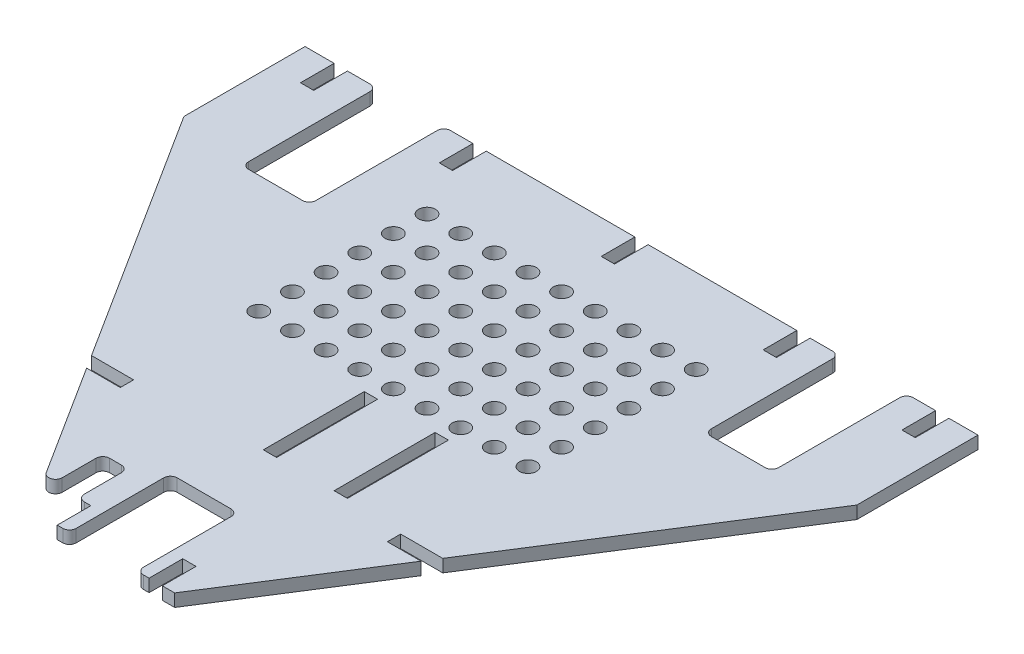
SolidWorks part; units mm, degrees
material "Corrugated Paper"
ref_plane "Front Plane" through (0, 0, 0) normal (0, 0, 1) x (1, 0, 0)
ref_plane "Top Plane" through (0, 0, 0) normal (0, 1, 0) x (1, 0, 0)
ref_plane "Right Plane" through (0, 0, 0) normal (1, 0, 0) x (0, 0, -1)
sketch "Sketch1" plane through (0, 0, 0) normal (0, 1, 0) x (1, 0, 0)
  line L0 (0, 0) -> (0, -142.875) construction
  line L1 (12.7, -63.5) -> (-12.7, -63.5)
  line L2 (-12.7, -63.5) -> (-12.7, -101.6)
  line L3 (-12.7, -101.6) -> (-17.3355, -101.6)
  line L4 (-26.9875, -101.6) -> (-127, 55.88)
  line L5 (-127, 55.88) -> (-127, 101.6)
  line L6 (-127, 101.6) -> (-116.0145, 101.6)
  line L7 (-100.0125, 101.6) -> (-100.0125, 50.8)
  line L9 (-100.0125, 50.8) -> (-74.6125, 50.8)
  line L10 (-74.6125, 50.8) -> (-74.6125, 101.6)
  line L11 (-74.6125, 101.6) -> (-63.627, 101.6)
  line L13 (74.6125, 50.8) -> (74.6125, 101.6)
  line L14 (100.0125, 50.8) -> (74.6125, 50.8)
  line L15 (100.0125, 101.6) -> (100.0125, 50.8)
  line L16 (127, 101.6) -> (116.0145, 101.6)
  line L17 (127, 55.88) -> (127, 101.6)
  line L18 (26.9875, -101.6) -> (127, 55.88)
  line L19 (12.7, -101.6) -> (17.3355, -101.6)
  line L20 (12.7, -63.5) -> (12.7, -101.6)
  line L21 (-127, 101.6) -> (127, -101.6) construction
  line L22 (-22.352, -101.6) -> (-26.9875, -101.6)
  line L24 (-22.352, -101.6) -> (-22.352, -88.9)
  line L25 (-22.352, -88.9) -> (-17.3355, -88.9)
  line L26 (-17.3355, -101.6) -> (-17.3355, -88.9)
  line L27 (22.352, -101.6) -> (22.352, -88.9)
  line L28 (22.352, -88.9) -> (17.3355, -88.9)
  line L29 (17.3355, -101.6) -> (17.3355, -88.9)
  line L30 (22.352, -101.6) -> (26.9875, -101.6)
  line L31 (-87.3125, 50.8) -> (-87.3125, 101.6) construction
  line L32 (-110.998, 101.6) -> (-100.0125, 101.6)
  line L34 (-116.0145, 101.6) -> (-116.0145, 88.9)
  line L35 (-116.0145, 88.9) -> (-110.998, 88.9)
  line L36 (-110.998, 101.6) -> (-110.998, 88.9)
  line L37 (-58.6105, 101.6) -> (-58.6105, 88.9)
  line L38 (-58.6105, 88.9) -> (-63.627, 88.9)
  line L39 (-63.627, 101.6) -> (-63.627, 88.9)
  line L40 (-58.6105, 101.6) -> (58.6105, 101.6)
  line L41 (116.0145, 101.6) -> (116.0145, 88.9)
  line L42 (116.0145, 88.9) -> (110.998, 88.9)
  line L43 (110.998, 101.6) -> (110.998, 88.9)
  line L44 (58.6105, 101.6) -> (58.6105, 88.9)
  line L45 (63.627, 101.6) -> (63.627, 88.9)
  line L46 (58.6105, 88.9) -> (63.627, 88.9)
  line L47 (63.627, 101.6) -> (74.6125, 101.6)
  line L48 (110.998, 101.6) -> (100.0125, 101.6)
  point P26 (0, -63.5)
  dimension "D2" = 25.4
  dimension "D3" = 254
  dimension "D5" = 38.1
  dimension "D6" = 50.8
  dimension "D7" = 203.2
  dimension "D8" = 45.72
  dimension "D9" = 26.9875
  dimension "D4" = 14.2875
  dimension "D10" = 5.0165
  dimension "D11" = 12.7
  dimension "D12" = 5.0165
extrude "Boss-Extrude1" add sketch "Sketch1" along normal blind 4.7625 contours L13 L47 L45 L46 L44 L40 L37 L38 L39 L11 L10 L9 L7 L32 L36 L35 L34 L6 L5 L4 L22 L24 L25 L26 L3 L2 L1 L20 L19 L29 L28 L27 L30 L18 L17 L16 L41 L42 L43 L48 L15 L14
sketch "Sketch2" plane through (0, 4.7625, 0) normal (0, 1, 0) x (1, 0, 0)
  line L0 (12.827, 0) -> (12.827, 54.8341) construction
  line L5 (-7.8105, -1021.0759) -> (-7.8105, 48978.9241) construction
  line L6 (-58.6105, 88.9) -> (-63.627, 88.9) construction
  line L7 (-3.048, 0) -> (1.9685, 0)
  line L8 (-3.048, 0) -> (-3.048, -38.1)
  line L9 (-3.048, -38.1) -> (1.9685, -38.1)
  line L10 (1.9685, 0) -> (1.9685, -38.1)
  line L11 (-22.352, -101.6) -> (-31.877, -101.6)
  line L12 (23.6855, 0) -> (23.6855, -38.1)
  line L13 (28.702, -38.1) -> (23.6855, -38.1)
  line L14 (28.702, 0) -> (28.702, -38.1)
  line L15 (28.702, 0) -> (23.6855, 0)
  line L16 (-22.352, -101.6) -> (-22.352, -69.85)
  line L17 (12.7, -63.5) -> (-12.7, -63.5) construction
  line L18 (-22.352, -69.85) -> (-31.877, -69.85)
  line L19 (-31.877, -101.6) -> (-31.877, -69.85)
  line L20 (-17.3355, -101.6) -> (-17.3355, -88.9) construction
  dimension "D2" = 25.4
  dimension "D3" = 31.75
  dimension "D1" = 38.1
  dimension "D5" = 9.525
  dimension "D6" = 31.75
  dimension "D7" = 9.525
  dimension "D4" = 9.525
extrude "Cut-Extrude1" cut sketch "Sketch2" against normal through all
fillet "Fillet1" radius 2.54 4 edges at (-22.352, 2.3813, 88.9) (-31.877, 2.3813, 93.901) (-22.352, 2.3813, 69.85) (-31.877, 2.3813, 69.85)
fillet "Fillet2" radius 2.54 12 edges at (-12.7, 2.3813, 101.6) (12.7, 2.3813, 101.6) (12.7, 2.3813, 63.5) (-12.7, 2.3813, 63.5) (100.0125, 2.3813, -101.6) (100.0125, 2.3813, -50.8) (74.6125, 2.3813, -101.6) (74.6125, 2.3813, -50.8) (-100.0125, 2.3813, -101.6) (-74.6125, 2.3813, -101.6) (-74.6125, 2.3813, -50.8) (-100.0125, 2.3813, -50.8)
sketch "Sketch3" plane through (0, 4.7625, 0) normal (0, 1, 0) x (1, 0, 0)
  line L0 (-74.6125, 53.34) -> (-74.6125, 99.06) construction
  line L1 (-58.6105, 88.9) -> (-63.627, 88.9) construction
  circle A0 centre (-49.2125, 69.85) radius 3.175
  dimension "D1" = 6.35
  dimension "D2" = 25.4
  dimension "D3" = 19.05
extrude "Cut-Extrude2" cut sketch "Sketch3" against normal through all
pattern_linear "LPattern1" count 9 spacing 12.7 along (1, 0, 0) count 6 spacing 12.7 along (0, 0, 1) of "Cut-Extrude2"
sketch "Sketch4" plane through (0, 4.7625, 0) normal (0, 1, 0) x (1, 0, 0)
  line L0 (0, -164.31) -> (0, 101.6) construction
  line L1 (-63.105, 101.6) -> (63.105, 101.6) construction
  line L2 (-63.105, 101.6) -> (-63.105, -164.31) construction
  line L3 (-63.105, -164.31) -> (63.105, -164.31) construction
  line L4 (63.105, 101.6) -> (63.105, -164.31) construction
  line L5 (26.9875, -101.6) -> (127, 55.88) construction
  line L6 (66.2909, -39.7128) -> (50.405, -39.7128)
  line L7 (66.2909, -39.7128) -> (66.2909, -44.7293)
  line L8 (66.2909, -44.7293) -> (50.405, -44.7293)
  line L9 (50.405, -39.7128) -> (50.405, -44.7293)
  line L10 (-50.405, -39.7128) -> (-50.405, -44.7293)
  line L11 (-66.2909, -44.7293) -> (-50.405, -44.7293)
  line L12 (-66.2909, -39.7128) -> (-66.2909, -44.7293)
  line L13 (-66.2909, -39.7128) -> (-50.405, -39.7128)
  line L14 (-58.6105, 101.6) -> (58.6105, 101.6) construction
  line L15 (-2.5082, 101.6) -> (2.5082, 101.6)
  line L16 (-2.5082, 101.6) -> (-2.5083, 88.9)
  line L17 (-2.5083, 88.9) -> (2.5083, 88.9)
  line L18 (2.5082, 101.6) -> (2.5083, 88.9)
  point P8 (63.105, -44.7293)
  point P11 (0, 101.6)
  dimension "D1" = 265.91
  dimension "D2" = 126.21
  dimension "D5" = 5.0165
  dimension "D6" = 12.7
  dimension "D4" = 12.7
  dimension "D3" = 5.0165
extrude "Cut-Extrude3" cut sketch "Sketch4" against normal through all
equation "\"D1@Boss-Extrude1\" = \"thick\""
equation "\"D4@Sketch1\" = \"thick\" * 3"
equation "\"D10@Sketch1\"=\"thick\"+\"clear\""
equation "\"D9@Sketch1\" = \"thick\" * 3 + 0.5"
equation "\"D12@Sketch1\"=\"thick\"+\"clear\""
equation "\"D3@Sketch2\"=\"MotorLength@Motor-1.Part\""
equation "\"D1@Sketch2\" =  ( \"MotorDiameter@Motor-1.Part\" + 0.5 ) "
equation "\"rodThick\"= 3/16in"
equation "\"thick\"= 3/16in"
equation "\"D5@Sketch2\"=2*\"thick\""
equation "\"clear\"= 0.01in"
equation "\"D7@Sketch2\"=2*\"thick\""
equation "\"D4@Sketch2\"=2*\"thick\""
equation "\"D5@Sketch4\"=\"thick\"+\"clear\""
